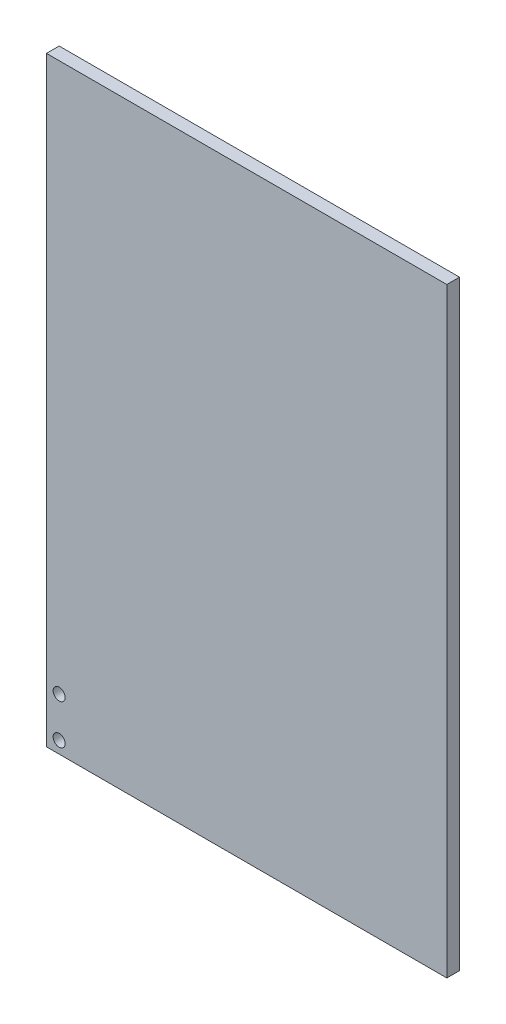
SolidWorks part; units mm, degrees
ref_plane "Front Plane" through (0, 0, 0) normal (0, 0, 1) x (1, 0, 0)
ref_plane "Top Plane" through (0, 0, 0) normal (0, 1, 0) x (1, 0, 0)
ref_plane "Right Plane" through (0, 0, 0) normal (1, 0, 0) x (0, 0, -1)
sketch "Sketch1" plane through (0, 0, 0) normal (0, 1, 0) x (1, 0, 0)
  line L1 (0, 0) -> (100, 0)
  line L2 (0, 0) -> (0, 3.175)
  line L3 (0, 3.175) -> (100, 3.175)
  line L4 (100, 0) -> (100, 3.175)
  dimension "D1" = 100
  dimension "D2" = 3.175
extrude "Boss-Extrude1" add sketch "Sketch1" along normal blind 150
sketch "Sketch2" plane through (0, 0, 0) normal (0, 0, 1) x (1, 0, 0)
  line L5 (0, 0) -> (6.35, 0)
  line L6 (0, 0) -> (0, 16)
  line L7 (0, 16) -> (6.35, 16)
  line L8 (6.35, 0) -> (6.35, 16)
  circle A3 centre (3.175, 13) radius 1.5
  circle A4 centre (3.175, 3) radius 1.5
  dimension "D5" = 3
  dimension "D6" = 3
  dimension "D7" = 3.175
  dimension "D3" = 3
  dimension "D4" = 3
  dimension "D1" = 6.35
  dimension "D2" = 16
  dimension "D8" = 3.175
extrude "Cut-Extrude2" cut sketch "Sketch2" against normal blind 3.175 contours A4 | A3 region at (3.175, 3, 0)
